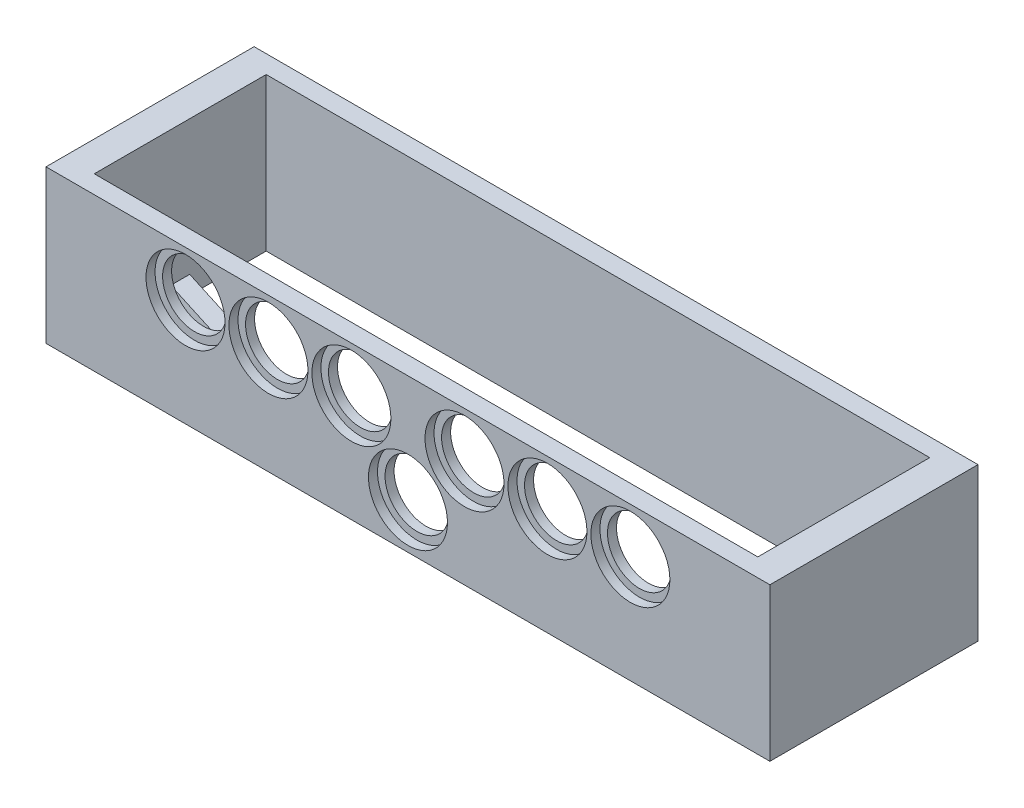
SolidWorks part; units mm, degrees
ref_plane "Přední rovina" through (0, 0, 0) normal (0, 0, 1) x (1, 0, 0)
ref_plane "Horní rovina" through (0, 0, 0) normal (0, 1, 0) x (1, 0, 0)
ref_plane "Pravá rovina" through (0, 0, 0) normal (1, 0, 0) x (0, 0, -1)
sketch "Skica1" plane through (0, 0, 0) normal (0, 1, 0) x (1, 0, 0)
  line L0 (0, 0) -> (240, 0)
  line L1 (240, 0) -> (240, 69)
  line L2 (240, 69) -> (0, 69)
  line L3 (0, 69) -> (0, 0)
  line L4 (10, 63) -> (10, 6)
  line L5 (10, 6) -> (230, 6)
  line L6 (230, 6) -> (230, 63)
  line L7 (230, 63) -> (10, 63)
  point P7 (231.607, 65.9498)
  dimension "D1" = 240
  dimension "D2" = 69
  dimension "D3" = 6
  dimension "D4" = 6
  dimension "D5" = 10
  dimension "D6" = 10
extrude "Přidat vysunutím1" add sketch "Skica1" along normal blind 50.7
sketch "Skica2" plane through (0, 0, 0) normal (0, 0, 1) x (1, 0, 0)
  line L0 (0, 50.7) -> (0, 0) construction
  line L1 (0, 50.7) -> (240, 50.7) construction
  line L2 (-15.8466, 35.6) -> (273.2323, 35.6) construction
  line L3 (240, 50.7) -> (240, 0) construction
  line L4 (0, 0) -> (240, 0) construction
  circle A0 centre (46.25, 35.6) radius 13.1
  circle A1 centre (73.75, 35.6) radius 13.1
  circle A2 centre (101.25, 35.6) radius 13.1
  circle A3 centre (138.75, 35.6) radius 13.1
  circle A4 centre (166.25, 35.6) radius 13.1
  circle A5 centre (193.75, 35.6) radius 13.1
  circle A6 centre (120, 15.1) radius 13.1
  dimension "D2" = 26.2
  dimension "D9" = 26.2
  dimension "D10" = 26.2
  dimension "D11" = 26.2
  dimension "D12" = 26.2
  dimension "D13" = 26.2
  dimension "D14" = 26.2
  dimension "D1" = 46.25
  dimension "D3" = 15.1
  dimension "D4" = 27.5
  dimension "D5" = 27.5
  dimension "D6" = 27.5
  dimension "D7" = 27.5
  dimension "D8" = 46.25
  dimension "D15" = 120
  dimension "D16" = 15.1
extrude "Odebrat vysunutím1" cut sketch "Skica2" against normal blind 3
sketch "Skica4" plane through (0, 0, 0) normal (0, 0, 1) x (1, 0, 0)
  circle A0 centre (46.25, 35.6) radius 10.6
  circle A1 centre (73.75, 35.6) radius 10.6
  circle A2 centre (138.75, 35.6) radius 10.6
  circle A3 centre (101.25, 35.6) radius 10.6
  circle A4 centre (120, 15.1) radius 10.6
  circle A5 centre (166.25, 35.6) radius 10.6
  circle A6 centre (193.75, 35.6) radius 10.6
  dimension "D1" = 21.2
extrude "Odebrat vysunutím2" cut sketch "Skica4" against normal blind 6
sketch "Skica5" plane through (0, 0, 0) normal (0, -1, 0) x (1, 0, 0)
  line L1 (0, -34.5) -> (110, 0)
  line L2 (0, 0) -> (240, 0) construction
  line L3 (0, -40.79) -> (130.0551, 0)
  line L4 (240, -34.5) -> (130, 0)
  line L5 (240, 0) -> (240, -69) construction
  line L6 (240, -40.79) -> (109.9449, 0)
  line L7 (0, -40.79) -> (0, -34.5)
  line L8 (110, 0) -> (130.0551, 0)
  line L9 (130, 0) -> (109.9449, 0)
  line L10 (240, -34.5) -> (240, -40.79)
  line L11 (0, -69) -> (0, 0) construction
  point P3 (240, -35.808)
  point P17 (0, -34.7987)
  line M8 (10, -63) -> (10, -6)
  line M9 (10, -6) -> (230, -6)
  line M10 (230, -6) -> (230, -63)
  dimension "D1" = 6.29
  dimension "D2" = 180
  dimension "D3" = 6.0017
  dimension "D4" = 110
  dimension "D5" = 110
  dimension "D6" = 6.29
  dimension "D7" = 180
  dimension "D8" = 6.0017
extrude "Přidat vysunutím2" add sketch "Skica5" against normal blind 6 contours L6 L4 M10 M9 | L3 L1 M8 M9 region at (55.6329, 0, -20.3121) region at (184.3671, 0, -20.3121)
